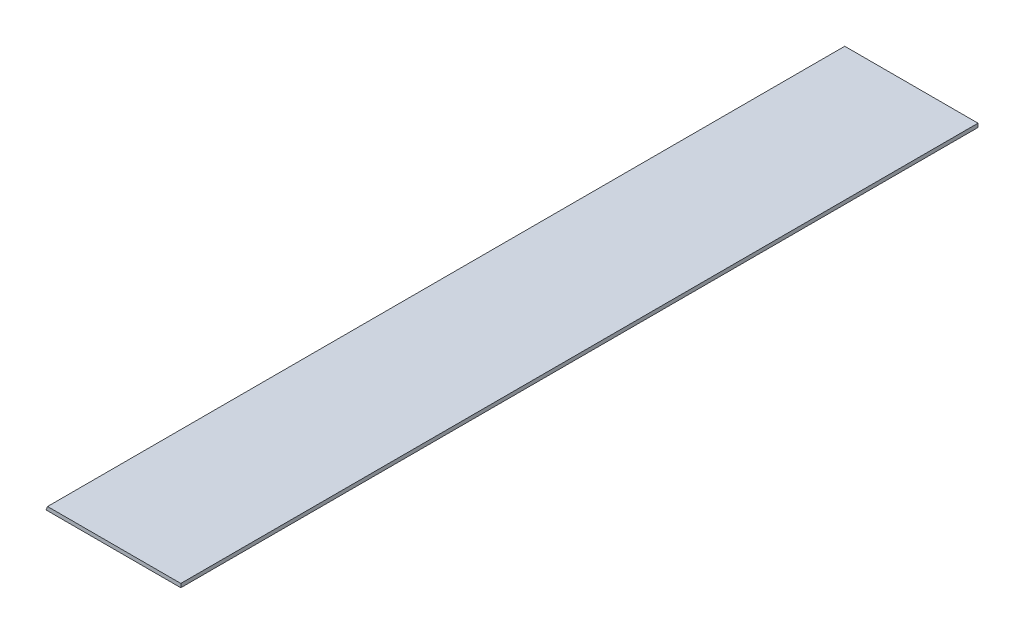
SolidWorks part; units mm, degrees
ref_plane "Front Plane" through (0, 0, 0) normal (0, 0, 1) x (1, 0, 0)
ref_plane "Top Plane" through (0, 0, 0) normal (0, 1, 0) x (1, 0, 0)
ref_plane "Right Plane" through (0, 0, 0) normal (1, 0, 0) x (0, 0, -1)
sketch "Sketch1" plane through (0, 0, 0) normal (0, 0, 1) x (1, 0, 0)
  line L0 (0, 0) -> (0.9785, 2.3622)
  line L1 (0.9785, 2.3622) -> (84.836, 2.3622)
  line L2 (84.836, 2.3622) -> (84.836, 0)
  line L3 (84.836, 0) -> (0, 0)
  dimension "D1" = 84.836
  dimension "D2" = 67.5
  dimension "D3" = 2.3622
extrude "Boss-Extrude1" add sketch "Sketch1" along normal blind 501.65
